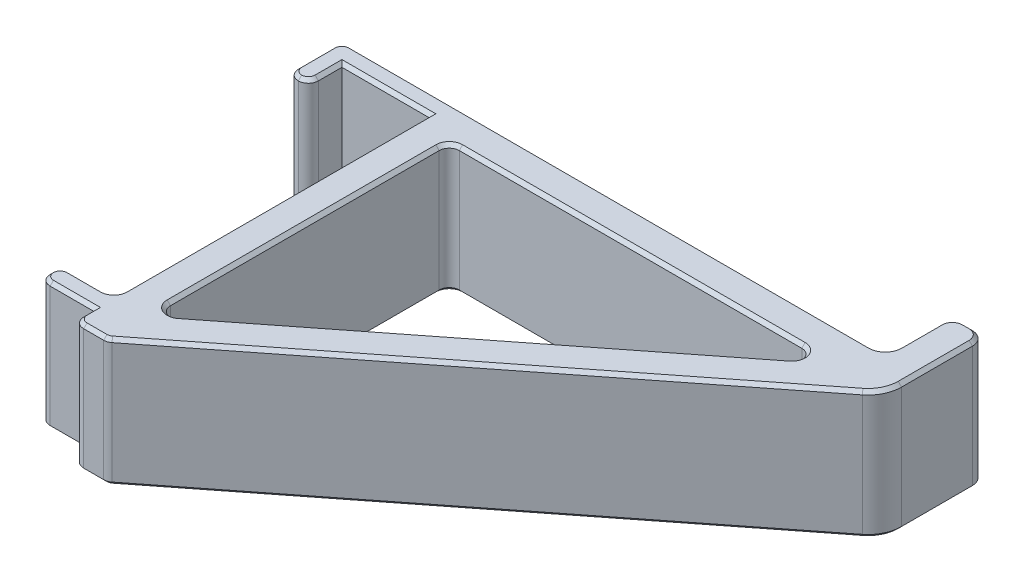
SolidWorks part; units mm, degrees
ref_plane "Front Plane" through (0, 0, 0) normal (0, 0, 1) x (1, 0, 0)
ref_plane "Top Plane" through (0, 0, 0) normal (0, 1, 0) x (1, 0, 0)
ref_plane "Right Plane" through (0, 0, 0) normal (1, 0, 0) x (0, 0, -1)
sketch "Sketch1" plane through (0, 0, 0) normal (0, 1, 0) x (1, 0, 0)
  line L2 (-47.9259, -7.5296) -> (-47.9259, 24.4704)
  line L3 (-47.9259, 27.4704) -> (17.0741, 27.4704)
  line L4 (22.0741, 22.4704) -> (22.0741, 27.4704)
  line L5 (-47.9259, 27.4704) -> (-63.9259, 27.4704)
  line L8 (-63.9259, 27.4704) -> (-63.9259, 24.4704)
  line L10 (-63.9259, 24.4704) -> (-63.9259, 19.4704)
  line L11 (-63.9259, 19.4704) -> (-60.9259, 19.4704)
  line L12 (-60.9259, 24.4704) -> (-60.9259, 19.4704)
  line L15 (-60.9259, 24.4704) -> (-47.9259, 24.4704)
  line L16 (-47.9259, -22.5296) -> (-47.9259, 24.4704)
  line L17 (-47.9259, -28.5296) -> (-42.9259, -28.5296)
  line L18 (-55.9259, -22.5296) -> (-47.9259, -22.5296)
  line L20 (-55.9259, -25.5296) -> (-47.9259, -25.5296)
  line L23 (-47.9259, -7.5296) -> (-47.9259, -22.5296)
  line L26 (-55.9259, -22.5296) -> (-55.9259, -25.5296)
  line L28 (-47.9259, -25.5296) -> (-47.9259, -28.5296)
  line L29 (-47.9259, -28.5296) -> (-42.9259, -28.5296)
  line L31 (-47.9259, -28.5296) -> (-47.9259, -25.5296)
  line L32 (-47.9259, 27.4704) -> (-42.9259, 27.4704)
  line L36 (-47.9259, 27.4704) -> (17.0741, 27.4704)
  line L37 (22.0741, 24.4704) -> (22.0741, 27.4704)
  line L38 (-13.5124, 0.9041) -> (13.9741, 22.4704)
  line L39 (-13.5124, 0.9041) -> (-42.9259, -22.1742)
  line L40 (22.0741, 22.4704) -> (-42.9259, -28.5296)
  line L41 (-42.9259, -22.1742) -> (-42.9259, 22.4704)
  line L42 (-42.9259, 22.4704) -> (13.9741, 22.4704)
  line L45 (22.0741, 27.4704) -> (22.0741, 37.4704)
  line L46 (22.0741, 37.4704) -> (17.0741, 37.4704)
  line L47 (17.0741, 27.4704) -> (17.0741, 37.4704)
  point P0 (0, 0)
  dimension "D1" = 70
  dimension "D2" = 10
  dimension "D3" = 13
  dimension "D4" = 3
  dimension "D5" = 3
  dimension "D6" = 5
  dimension "D7" = 5
  dimension "D8" = 5
extrude "Boss-Extrude1" add sketch "Sketch1" along normal blind 19 contours L47 L3 L5 L8 L10 L11 L12 L15 L2 L16 L18 L26 L20 L28 L17 L40 L4 L45 L46 L41 L42 L38 L39
fillet "Fillet1" radius 1.5 11 edges at (13.9741, 9.5, -22.4704) (-42.9259, 9.5, -22.4704) (-42.9259, 9.5, 22.1742) (-47.9259, 9.5, 28.5296) (-55.9259, 9.5, 25.5296) (-55.9259, 9.5, 22.5296) (-47.9259, 9.5, 22.5296) (-63.9259, 9.5, -27.4704) (-63.9259, 9.5, -19.4704) (-60.9259, 9.5, -19.4704) (-42.9259, 9.5, 28.5296)
fillet "Fillet2" radius 2 3 edges at (22.0741, 9.5, -37.4704) (17.0741, 9.5, -37.4704) (17.0741, 9.5, -27.4704)
fillet "Fillet3" radius 5 1 edges at (22.0741, 9.5, -22.4704)
chamfer "Chamfer1" distance 0.5 angle 45 62 edges at (-42.4866, 0, -22.0311) (-15.8968, 0, -22.4704) (11.0501, 0, -21.4602) (-14.9709, 0, 0.2402) (-42.0821, 0, 20.4396) (-42.9259, 0, -0.9399) (21.4883, 0, -36.8846) (19.5741, 0, -37.4704) (17.6599, 0, -36.8846) (17.0741, 0, -32.4704) (16.4883, 0, -28.0562) (-23.6759, 0, -27.4704) (-63.4866, 0, -27.0311) (-63.9259, 0, -23.4704) (-63.4866, 0, -19.9098) (-61.3653, 0, -19.9098) (-60.9259, 0, -22.7204) (-54.4259, 0, -24.4704) (-47.9259, 0, -1.7204) (-48.3653, 0, 22.0902) (-51.9259, 0, 22.5296) (-55.4866, 0, 22.9689) (-55.4866, 0, 25.0902) (-51.1759, 0, 25.5296) (-47.9259, 0, 26.2796) (-47.4866, 0, 28.0902) (-44.935, 0, 28.5296) (-42.9543, 0, 28.4474) (-11.1789, 0, 3.6203) (21.5703, 0, -22.7155) (22.0741, 0, -30.1866) (11.0501, 19, -21.4602) (-15.8968, 19, -22.4704) (-42.4866, 19, -22.0311) (-42.9259, 19, -0.9399) (-42.0821, 19, 20.4396) (-14.9709, 19, 0.2402) (-42.9543, 19, 28.4474) (-44.935, 19, 28.5296) (-47.4866, 19, 28.0902) (-47.9259, 19, 26.2796) (-51.1759, 19, 25.5296) (-55.4866, 19, 25.0902) (-55.4866, 19, 22.9689) (-51.9259, 19, 22.5296) (-48.3653, 19, 22.0902) (-47.9259, 19, -1.7204) (-54.4259, 19, -24.4704) (-60.9259, 19, -22.7204) (-61.3653, 19, -19.9098) (-63.4866, 19, -19.9098) (-63.9259, 19, -23.4704) (-63.4866, 19, -27.0311) (-23.6759, 19, -27.4704) (16.4883, 19, -28.0562) (17.0741, 19, -32.4704) (17.6599, 19, -36.8846) (19.5741, 19, -37.4704) (21.4883, 19, -36.8846) (22.0741, 19, -30.1866) (21.5703, 19, -22.7155) (-11.1789, 19, 3.6203)
